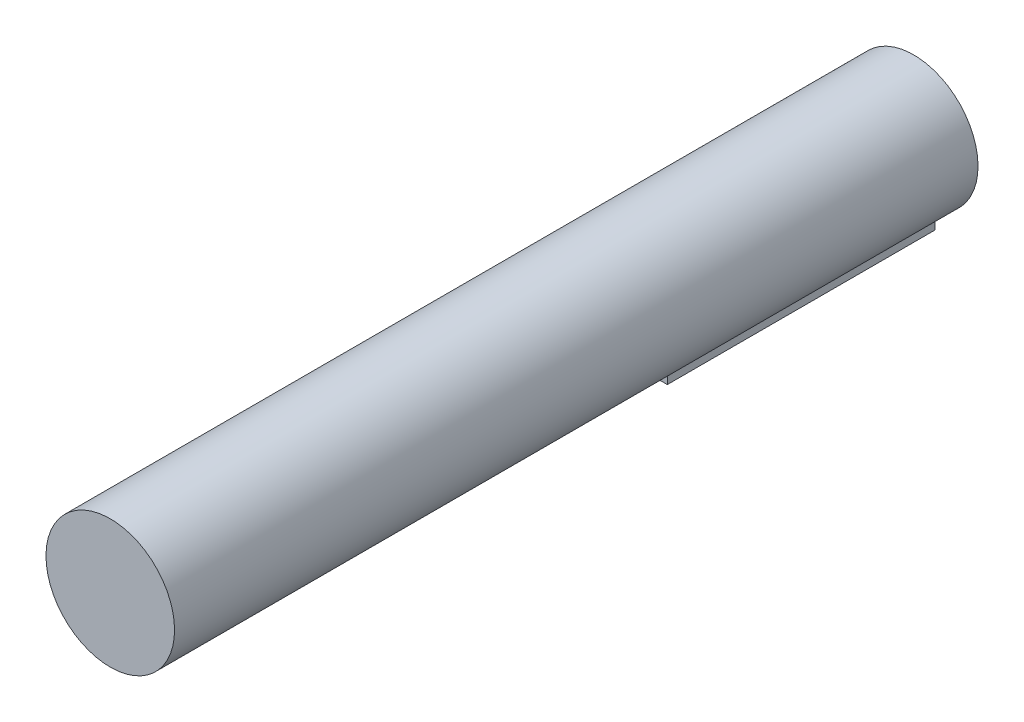
SolidWorks part; units mm, degrees
ref_plane "Plano frontal" through (0, 0, 0) normal (0, 0, 1) x (1, 0, 0)
ref_plane "Plano superior" through (0, 0, 0) normal (0, 1, 0) x (1, 0, 0)
ref_plane "Plano direito" through (0, 0, 0) normal (1, 0, 0) x (0, 0, -1)
sketch "Esboço2" plane through (0, 0, 0) normal (0, 0, 1) x (1, 0, 0)
  line L0 (4, -11.3137) -> (4, -14.3137)
  line L1 (4, -14.3137) -> (-4, -14.3137)
  line L2 (-4, -14.3137) -> (-4, -11.3137)
  circle A0 centre (0, 0) radius 12
  point P5 (0, -14.3137)
  dimension "D1" = 24
  dimension "D2" = 3
  dimension "D3" = 8
extrude "Ressalto-extrusão4" add sketch "Esboço2" along normal blind 50 contours A0 L2 L1 L0 region at (0, -13.0356, 0)
extrude "Ressalto-extrusão5" add sketch "Esboço2<3>" along normal blind 150 contours A0 region at (0, 0, 0)
sketch "Esboço2<3>" plane through (0, 0, 0) normal (0, 0, 1) x (1, 0, 0) same geometry as "Esboço2"
